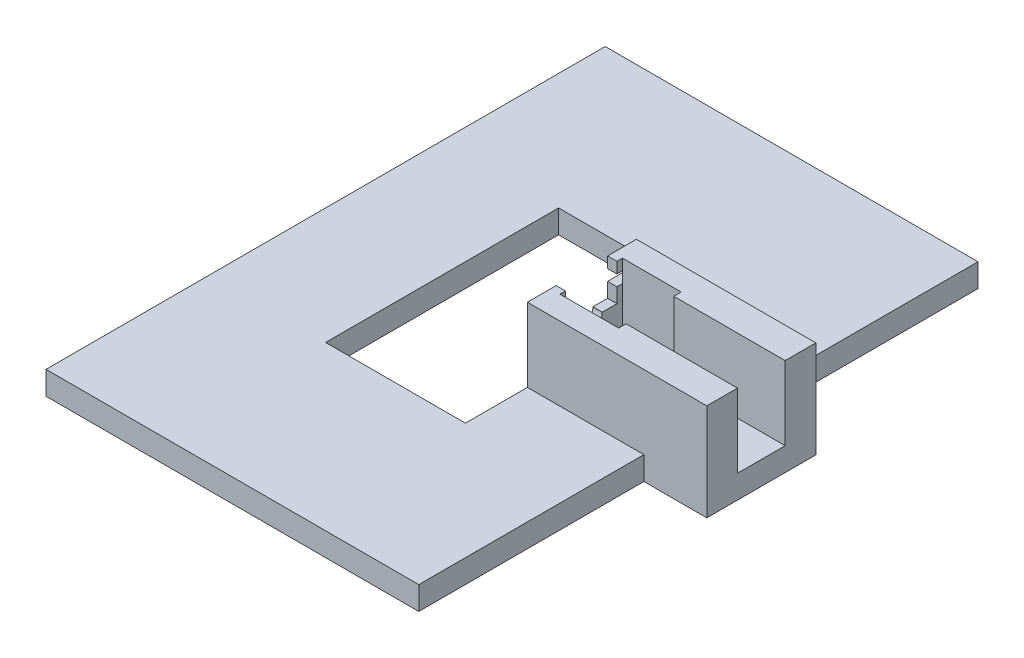
SolidWorks part; units mm, degrees
ref_plane "Front Plane" through (0, 0, 0) normal (0, 0, 1) x (1, 0, 0)
ref_plane "Top Plane" through (0, 0, 0) normal (0, 1, 0) x (1, 0, 0)
ref_plane "Right Plane" through (0, 0, 0) normal (1, 0, 0) x (0, 0, -1)
sketch "Sketch1" plane through (0, 0, 0) normal (0, 1, 0) x (1, 0, 0)
  line L1 (-50.8, -76.2) -> (50.8, -76.2)
  line L2 (-50.8, -76.2) -> (-50.8, 76.2)
  line L3 (-50.8, 76.2) -> (50.8, 76.2)
  line L4 (50.8, -76.2) -> (50.8, 76.2)
  line L5 (-50.8, -76.2) -> (50.8, 76.2) construction
  line L6 (-50.8, 76.2) -> (50.8, -76.2) construction
  point P0 (0, 0)
  dimension "D1" = 152.4
  dimension "D2" = 101.6
extrude "Boss-Extrude1" add sketch "Sketch1" against normal blind 6.35
sketch "Sketch2" plane through (0, 0, 0) normal (0, 1, 0) x (1, 0, 0)
  line L1 (-19.05, -31.75) -> (19.05, -31.75)
  line L2 (-19.05, -31.75) -> (-19.05, 31.75)
  line L3 (-19.05, 31.75) -> (19.05, 31.75)
  line L4 (19.05, -31.75) -> (19.05, 31.75)
  line L5 (-19.05, -31.75) -> (19.05, 31.75) construction
  line L6 (-19.05, 31.75) -> (19.05, -31.75) construction
  point P0 (0, 0)
  dimension "D1" = 38.1
  dimension "D2" = 63.5
extrude "Cut-Extrude1" cut sketch "Sketch2" against normal through all
sketch "Sketch4" plane through (0, 0, 0) normal (0, 1, 0) x (1, 0, 0)
  line L0 (19.05, -31.75) -> (19.05, 31.75) construction
  line L1 (21.59, -8.509) -> (50.8, -8.509)
  line L3 (21.59, 8.509) -> (50.8, 8.509)
  line L4 (50.8, -8.509) -> (50.8, 8.509)
  line L5 (21.59, -8.509) -> (50.8, 8.509) construction
  line L6 (50.8, -8.509) -> (21.59, 8.509) construction
  line L7 (50.8, -76.2) -> (50.8, 76.2) construction
  line L9 (19.05, 14.859) -> (19.05, -14.859)
  line L10 (19.05, 14.859) -> (50.8, 14.859)
  line L11 (50.8, 14.859) -> (50.8, 8.509)
  line L12 (21.59, 8.509) -> (21.59, -8.509)
  line L13 (50.8, 8.509) -> (61.595, 8.509)
  line L14 (19.05, -14.859) -> (50.8, -14.859)
  line L15 (61.595, 8.509) -> (61.595, -8.509)
  line L16 (61.595, -8.509) -> (50.8, -8.509)
  line L17 (50.8, 14.859) -> (67.945, 14.859)
  line L18 (67.945, 14.859) -> (67.945, -14.859)
  line L19 (67.945, -14.859) -> (50.8, -14.859)
  point P0 (19.05, 0)
  point P2 (36.195, 0)
  line M13 (19.05, 31.75) -> (19.05, -31.75)
  line M16 (50.8, -76.2) -> (50.8, 76.2)
  dimension "D1" = 17.018
  dimension "D2" = 6.35
  dimension "D3" = 6.35
  dimension "D4" = 2.54
  dimension "D5" = 40.005
  dimension "D6" = 6.35
extrude "Boss-Extrude3" add sketch "Sketch4" against normal through all and the other way blind 10.0965 contours L19 L18 L17 L13 L15 L16 M16 | L14 L1 L12 L3 L10 M13 M16 region at (36.195, 0, 8.9439) region at (56.1975, 0, 8.8521)
sketch "Sketch6" plane through (19.05, 0, 0) normal (-1, 0, 0) x (0, 0, 1)
  line L0 (-14.859, 10.0965) -> (14.859, 10.0965) construction
  circle A0 centre (0, 10.0965) radius 3
  dimension "D1" = 6
extrude "Cut-Extrude2" cut sketch "Sketch6" against normal up to next
sketch "Sketch7" plane through (0, 10.0965, 0) normal (0, 1, 0) x (1, 0, 0)
  line L0 (21.59, 8.509) -> (37.59, 8.509) construction
  line L1 (21.59, 8.509) -> (61.595, 8.509) construction
  line L2 (37.59, 8.509) -> (37.59, 6.5)
  line L3 (37.59, 6.5) -> (61.595, 6.5)
  line L4 (61.595, 8.509) -> (61.595, -8.509) construction
  line L5 (61.595, 6.5) -> (61.595, -6.5)
  line L6 (61.595, -6.5) -> (37.59, -6.5)
  line L7 (37.59, -6.5) -> (37.59, -8.509)
  line L8 (61.595, -8.509) -> (21.59, -8.509) construction
  line L9 (37.59, -8.509) -> (61.595, -8.509)
  line L10 (61.595, -8.509) -> (61.595, -6.5)
  line L11 (61.595, 6.5) -> (61.595, 8.509)
  line L12 (61.595, 8.509) -> (37.59, 8.509)
  line L13 (21.59, 8.509) -> (21.59, 3) construction
  line M8 (21.59, 8.509) -> (61.595, 8.509)
  line M9 (61.595, 8.509) -> (61.595, -8.509)
  dimension "D1" = 13
  dimension "D2" = 16
  dimension "D3" = 24.005
extrude "Boss-Extrude4" add sketch "Sketch7" against normal through all contours L2 L3 M9 M8 | L6 L7 L9 L10 region at (49.5925, 10.0965, -7.5045)
sketch "Sketch10" plane through (50.8, 0, 0) normal (1, 0, 0) x (0, 0, -1)
  line L1 (-6.5, -6.35) -> (6.5, -6.35)
  line L2 (-6.5, -6.35) -> (-6.5, 0)
  line L3 (-6.5, 0) -> (6.5, 0)
  line L4 (6.5, -6.35) -> (6.5, 0)
extrude "Boss-Extrude5" add sketch "Sketch10" along normal through all
sketch "Sketch11" plane through (61.595, 0, 0) normal (-1, 0, 0) x (0, 0, 1)
  line L1 (6.5, 0) -> (-6.5, 0)
  line L2 (6.5, 0) -> (6.5, 10.0965)
  line L3 (6.5, 10.0965) -> (-6.5, 10.0965)
  line L4 (-6.5, 0) -> (-6.5, 10.0965)
extrude "Cut-Extrude3" cut sketch "Sketch11" against normal up to next
sketch "Sketch12" plane through (0, 10.0965, 0) normal (0, 1, 0) x (1, 0, 0)
  line L0 (67.945, -14.859) -> (67.945, -6.5) construction
  line L1 (67.945, -6.5) -> (37.59, -6.5) construction
  line L2 (37.59, -6.5) -> (37.59, -8.509) construction
  line L3 (37.59, -8.509) -> (21.59, -8.509) construction
  line L4 (21.59, -8.509) -> (21.59, -3) construction
  line L5 (21.59, -3) -> (19.05, -3) construction
  line L6 (19.05, -3) -> (19.05, -14.859) construction
  line L7 (19.05, -14.859) -> (67.945, -14.859) construction
  line L8 (37.59, 6.5) -> (67.945, 6.5) construction
  line L9 (67.945, 6.5) -> (67.945, 14.859) construction
  line L10 (67.945, 14.859) -> (19.05, 14.859) construction
  line L11 (19.05, 14.859) -> (19.05, 3) construction
  line L12 (19.05, 3) -> (21.59, 3) construction
  line L13 (21.59, 3) -> (21.59, 8.509) construction
  line L14 (21.59, 8.509) -> (37.59, 8.509) construction
  line L15 (37.59, 8.509) -> (37.59, 6.5) construction
  line L16 (67.945, -14.859) -> (67.945, -6.5)
  line L17 (67.945, -6.5) -> (37.59, -6.5)
  line L18 (37.59, -6.5) -> (37.59, -8.509)
  line L19 (37.59, -8.509) -> (21.59, -8.509)
  line L20 (21.59, -8.509) -> (21.59, -3)
  line L21 (21.59, -3) -> (19.05, -3)
  line L22 (19.05, -3) -> (19.05, -14.859)
  line L23 (19.05, -14.859) -> (67.945, -14.859)
  line L24 (37.59, 6.5) -> (67.945, 6.5)
  line L25 (67.945, 6.5) -> (67.945, 14.859)
  line L26 (67.945, 14.859) -> (19.05, 14.859)
  line L27 (19.05, 14.859) -> (19.05, 3)
  line L28 (19.05, 3) -> (21.59, 3)
  line L29 (21.59, 3) -> (21.59, 8.509)
  line L30 (21.59, 8.509) -> (37.59, 8.509)
  line L31 (37.59, 8.509) -> (37.59, 6.5)
extrude "Boss-Extrude6" add sketch "Sketch12" along normal blind 10
sketch "Sketch13" plane through (19.05, 0, 0) normal (-1, 0, 0) x (0, 0, 1)
  line L0 (3, 10.0965) -> (7, 10.0965)
  line L1 (7, 10.0965) -> (7, 14.0965)
  line L2 (7, 14.0965) -> (11, 14.0965)
  line L3 (11, 14.0965) -> (11, 17.0965)
  line L4 (11, 17.0965) -> (7, 17.0965)
  line L5 (7, 17.0965) -> (7, 20.0965)
  line L6 (3, 20.0965) -> (14.859, 20.0965) construction
  line L7 (7, 20.0965) -> (3, 20.0965)
  line L8 (3, 20.0965) -> (3, 10.0965)
  arc A0 (-3, 10.0965) -> (3, 10.0965) centre (0, 10.0965) ccw construction
  arc A1 (-3, 10.0965) -> (3, 10.0965) centre (0, 10.0965) ccw construction
  dimension "D1" = 4
  dimension "D2" = 4
  dimension "D3" = 3
  dimension "D4" = 4
extrude "Cut-Extrude4" cut sketch "Sketch13" against normal up to surface (2.54 mm away) up to face at (21.59, 12.1974, 0)
mirror "Mirror1" about plane through (0, 0, 0) normal (0, 0, 1) of "Cut-Extrude4"
